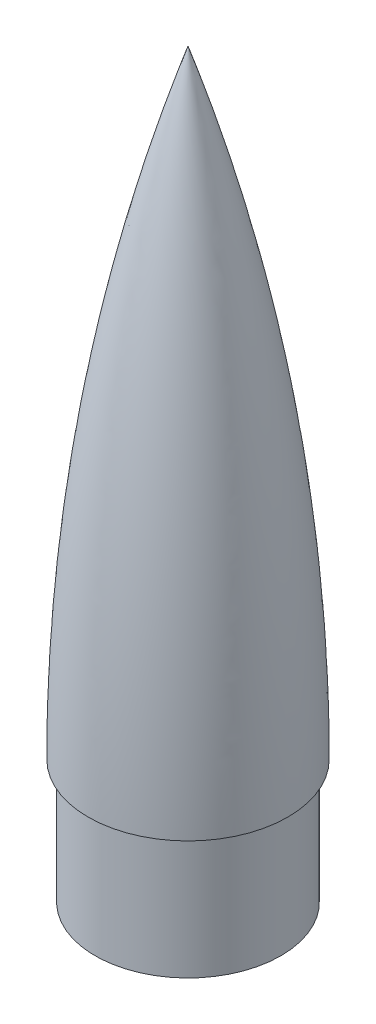
SolidWorks part; units mm, degrees
other "Nosecone"
ref_plane "Front Plane" through (0, 0, 0) normal (0, 0, 1) x (1, 0, 0)
ref_plane "Top Plane" through (0, 0, 0) normal (0, 1, 0) x (1, 0, 0)
ref_plane "Right Plane" through (0, 0, 0) normal (1, 0, 0) x (0, 0, -1)
sketch "Sketch3" plane through (0, 0, 0) normal (0, 0, 1) x (1, 0, 0)
  line L0 (0, 152.4) -> (0, 0)
  line L3 (-20.5232, 25.4) -> (20.5232, 25.4)
  line L5 (-20.5232, 25.4) -> (-20.5232, 152.4) construction
  line L7 (-19.1008, 25.4) -> (-19.1008, 0)
  line L8 (-19.1008, 0) -> (19.1008, 0)
  line L9 (19.1008, 0) -> (19.1008, 25.4)
  arc A0 (-20.5232, 25.4) -> (0, 152.4) centre (382.6839, 25.4) cw
  arc A1 (20.5232, 25.4) -> (0, 152.4) centre (-382.6839, 25.4) ccw
  dimension "D3" = 127
  dimension "D4" = 25.4
  dimension "D1" = 38.2016
  dimension "D2" = 41.0464
revolve "Revolve3" add sketch "Sketch3" angle 360 about L0 region at (8.2275, 73.1909, 0) region at (9.5504, 12.7, 0)
